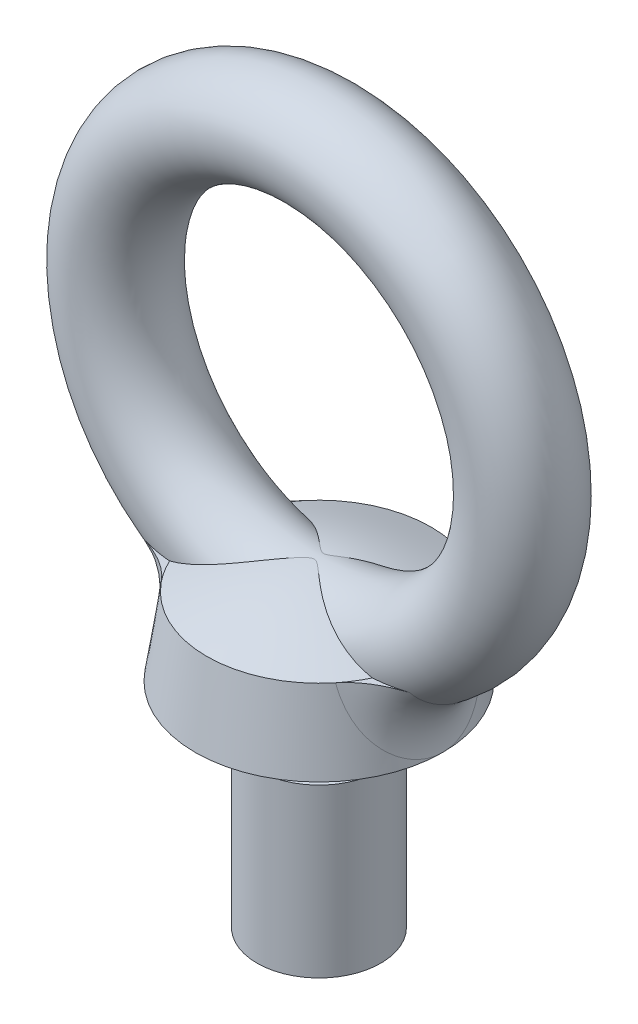
SolidWorks part; units mm, degrees
ref_plane "Front Plane" through (0, 0, 0) normal (0, 0, 1) x (1, 0, 0)
ref_plane "Top Plane" through (0, 0, 0) normal (0, 1, 0) x (1, 0, 0)
ref_plane "Right Plane" through (0, 0, 0) normal (1, 0, 0) x (0, 0, -1)
sketch "Sketch1" plane through (0, 0, 0) normal (0, 0, 1) x (1, 0, 0)
  line L0 (0, 0) -> (0, -80.1248) construction
  line L1 (0, -12) -> (7.249, -12)
  line L2 (7.249, -12) -> (8, -17)
  line L3 (8, -17) -> (4, -17)
  line L4 (4, -20) -> (4, -30.8)
  line L5 (0, -12) -> (0, -32)
  line L6 (3, -19) -> (3, -18)
  line L7 (4, -20) -> (-10.8447, -20) construction
  circle A0 centre (0, 0) radius 16.3 construction
  arc A1 (3, -19) -> (4, -20) centre (4, -19) ccw
  arc A2 (9.5998, -13.1732) -> (8, -17) centre (11.9556, -16.4059) ccw construction
  arc A3 (4, -17) -> (3, -18) centre (4, -18) ccw
  arc A4 (0, -32) -> (4, -30.8) centre (0, -24.7333) ccw
  point P21 (3, -20)
  dimension "D2" = 16
revolve "Revolve1" add sketch "Sketch1" angle 360 about L0
cosmetic thread "ThreadCosmetic1" [suppressed] parameters "dp"=6.619
sketch "Sketch2" plane through (0, 0, 0) normal (0, 0, 1) x (1, 0, 0)
  circle A0 centre (0, 0) radius 16.3 construction
  circle A1 centre (0, 0) radius 16.3 construction
  circle A2 centre (0, 0) radius 10
  dimension "b" = 20
sketch "Sketch3" plane through (0, 0, 0) normal (0, 1, 0) x (1, 0, 0)
  circle A0 centre (-13.15, 0) radius 3.15
  point P2 (-16.3, 0)
  point P3 (-10, 0)
sweep "Sweep1" add profiles "Sketch3" path "Sketch2"
fillet "Fillet2" radius 4 2 edges at (7.6009, -14.397, -0.3517) (-7.6009, -14.397, 0.3517)
sketch "Sketch4" plane through (0, 0, 0) normal (1, 0, 0) x (0, 0, -1)
  line L0 (0, -10.01) -> (-5.2122, -10.01) construction
  line L9 (0, -7.267) -> (0, -17.3967) construction
  line L10 (7.249, -12) -> (0, -12)
  line L11 (0, -10.01) -> (0, -12)
  spline S0 degree 3 poles (0, -10.01) (2.4461, -10.01) (4.8476, -11.005) (7.249, -12) knots 0 0 0 0 1 1 1 1
  point P5 (0, -10)
  dimension "D1" = 0.01
revolve "Revolve2" add sketch "Sketch4" angle 360 about L9
sketch "Sketch5" plane through (0, 0, 0) normal (0, 0, 1) x (1, 0, 0)
  line L0 (-4.6905, -19.6548) -> (-4, -19.6548)
  line L1 (-4, -19.6548) -> (-3.402, -20)
  line L2 (-3.402, -20) -> (-4, -20.3453)
  line L3 (-4, -20.3453) -> (-4.6905, -20.3453)
  line L4 (-4.6905, -20.3453) -> (-4.6905, -19.6548)
  line L5 (4, -20) -> (-4, -20) construction
  line L6 (-4, -20) -> (-4, -30.8) construction
  line L7 (0, -18.4833) -> (0, -25.3769) construction
  dimension "D1" = 0.6905
revolve "Cut-Revolve10" [suppressed] cut sketch "Sketch5" angle 360 about L7
pattern_linear "LPattern10" [suppressed] count 14 spacing 0.8286 along (0, -1, 0) of bodies 109
equation "\"D1@Sketch5\"= ( \"d@Sketch1\"-\"dp@ThreadCosmetic1\" )  / 2"
equation "\"D3@LPattern10\"=\"D1@Sketch5\" * 1.2"
equation "\"D1@LPattern10\" = (  \"l@Sketch1\" - \"e@Sketch1\" )  / \"D3@LPattern10\""
